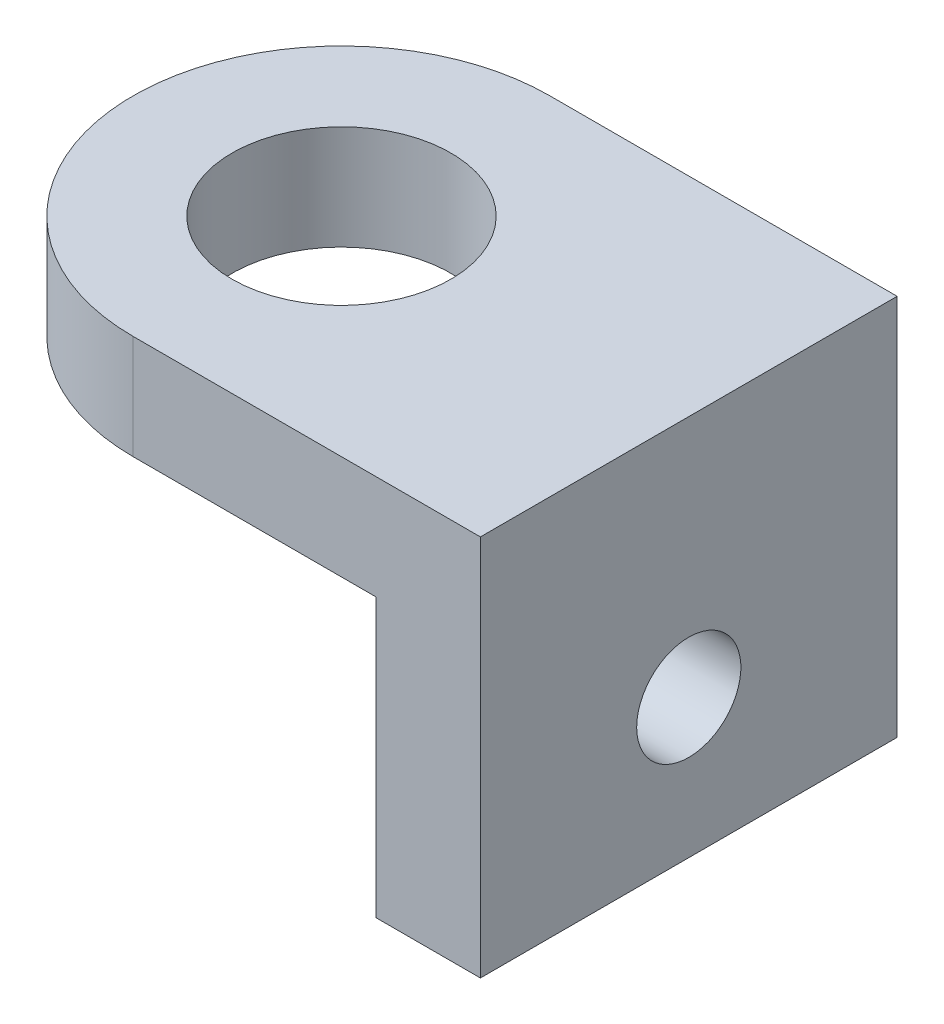
SolidWorks part; units mm, degrees
ref_plane "Front Plane" through (0, 0, 0) normal (0, 0, 1) x (1, 0, 0)
ref_plane "Top Plane" through (0, 0, 0) normal (0, 1, 0) x (1, 0, 0)
ref_plane "Right Plane" through (0, 0, 0) normal (1, 0, 0) x (0, 0, -1)
sketch "Sketch2" plane through (0, 0, 0) normal (0, 1, 0) x (1, 0, 0)
  line L0 (0, 0) -> (10, 0) construction
  line L1 (0, 6) -> (10, 6)
  line L2 (0, -6) -> (10, -6)
  line L3 (10, 6) -> (10, -6)
  line L4 (7, 6) -> (7, -6)
  arc A0 (0, 6) -> (0, -6) centre (0, 0) ccw
  circle A2 centre (0, 0) radius 3.15
  point P3 (5, 0)
  dimension "D1" = 6
  dimension "D2" = 6.3
  dimension "D3" = 10
  dimension "D4" = 3
extrude "Boss-Extrude1" add sketch "Sketch2" along normal blind 3 contours A2 L4 L1 A0 L2 | L4 L0 L3 L1 | L0 L4 L2 L3 region at (6.8231, 0, 3) region at (8.5, 0, -3) region at (8.5, 0, 3)
extrude "Boss-Extrude2" add sketch "Sketch2<3>" against normal blind 8 contours L4 L0 L3 L1 | L0 L4 L2 L3 region at (8.5, 0, -3) region at (8.5, 0, 3)
sketch "Sketch2<3>" plane through (0, 0, 0) normal (0, 1, 0) x (1, 0, 0) same geometry as "Sketch2"
sketch "Sketch4" plane through (7, 0, 0) normal (-1, 0, 0) x (0, 0, 1)
  line L0 (-6, 0) -> (6, 0) construction
  circle A0 centre (0, -4) radius 1.5
  point P4 (0, 0)
  point P6 (0, 0)
  dimension "D2" = 3
  dimension "D1" = 4
extrude "Cut-Extrude1" cut sketch "Sketch4" against normal through all
